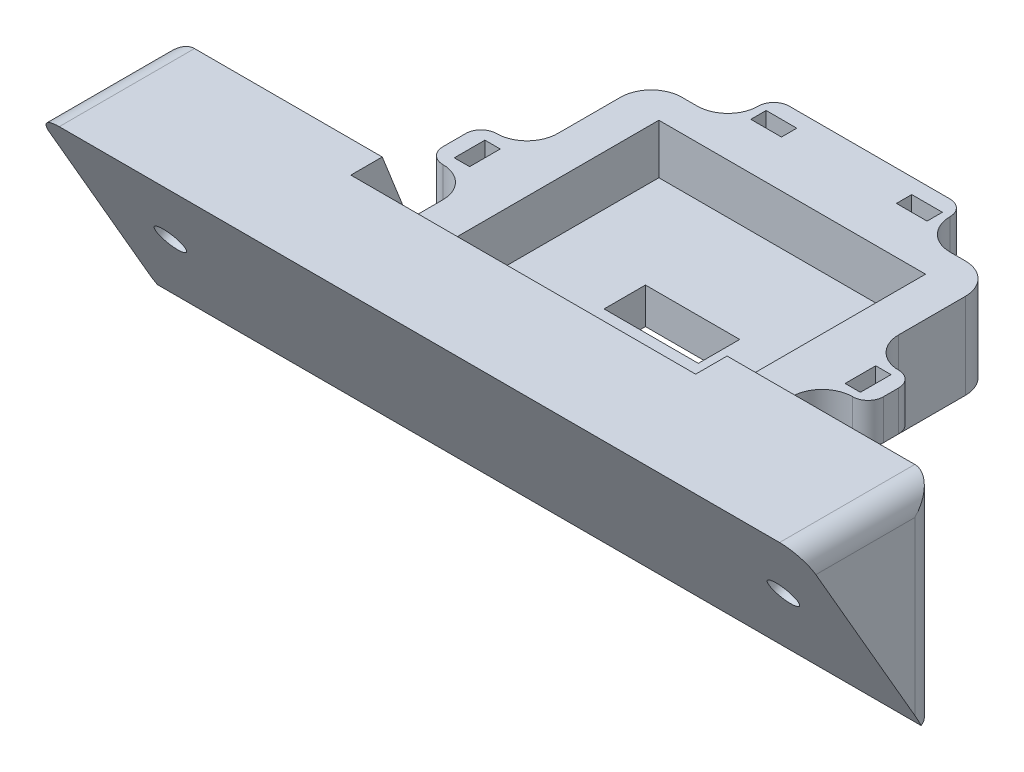
SolidWorks part; units mm, degrees
ref_plane "Front Plane" through (0, 0, 0) normal (0, 0, 1) x (1, 0, 0)
ref_plane "Top Plane" through (0, 0, 0) normal (0, 1, 0) x (1, 0, 0)
ref_plane "Right Plane" through (0, 0, 0) normal (1, 0, 0) x (0, 0, -1)
sketch "Sketch2" plane through (0, 0, 0) normal (0, 1, 0) x (1, 0, 0)
  line L1 (0, 0) -> (57.15, 0)
  line L2 (0, 0) -> (0, 49.784)
  line L3 (0, 49.784) -> (57.15, 49.784)
  line L4 (57.15, 0) -> (57.15, 49.784)
  dimension "D1" = 57.15
  dimension "D2" = 49.784
extrude "Boss-Extrude1" add sketch "Sketch2" along normal blind 14.224
sketch "Sketch3" plane through (0, 14.224, 0) normal (0, 1, 0) x (1, 0, 0)
  line L0 (0, 49.784) -> (0, 0) construction
  line L1 (6.477, 44.577) -> (50.673, 44.577)
  line L2 (6.477, 44.577) -> (6.477, 5.207)
  line L3 (6.477, 5.207) -> (50.673, 5.207)
  line L4 (50.673, 44.577) -> (50.673, 5.207)
  line L5 (57.15, 49.784) -> (0, 49.784) construction
  point P6 (0, 24.892)
  point P7 (6.477, 24.892)
  point P10 (28.575, 49.784)
  point P11 (28.575, 44.577)
  dimension "D1" = 44.196
  dimension "D2" = 39.37
extrude "Cut-Extrude1" cut sketch "Sketch3" against normal blind 8.255
sketch "Sketch4" plane through (0, 5.969, 0) normal (0, 1, 0) x (1, 0, 0)
  line L1 (10.795, 14.605) -> (46.355, 14.605)
  line L2 (10.795, 14.605) -> (10.795, 10.414)
  line L3 (10.795, 10.414) -> (46.355, 10.414)
  line L4 (46.355, 14.605) -> (46.355, 10.414)
  line L6 (6.477, 5.207) -> (50.673, 5.207) construction
  line L7 (50.673, 44.577) -> (6.477, 44.577) construction
  line L8 (20.7645, 28.067) -> (36.3855, 28.067)
  line L9 (20.7645, 28.067) -> (20.7645, 21.209)
  line L10 (20.7645, 21.209) -> (36.3855, 21.209)
  line L11 (36.3855, 28.067) -> (36.3855, 21.209)
  line L12 (6.477, 5.207) -> (50.673, 5.207) construction
  point P6 (28.575, 5.207)
  point P7 (28.575, 10.414)
  point P10 (28.575, 21.209)
  point P15 (28.575, 14.605)
  dimension "D1" = 35.56
  dimension "D3" = 9.398
  dimension "D4" = 4.191
  dimension "D5" = 15.621
  dimension "D6" = 6.858
  dimension "D7" = 16.51
extrude "Cut-Extrude2" cut sketch "Sketch4" against normal blind 8.255
sketch "Sketch5" plane through (0, 14.224, 0) normal (0, 1, 0) x (1, 0, 0)
  line L0 (0, 49.784) -> (0, 0) construction
  line L5 (57.15, 49.784) -> (0, 49.784) construction
  line L6 (0, 29.21) -> (-7.62, 29.21)
  line L7 (0, 29.21) -> (0, 20.32)
  line L8 (0, 20.32) -> (-7.62, 20.32)
  line L9 (-7.62, 29.21) -> (-7.62, 20.32)
  line L10 (12.7, 49.784) -> (36.83, 49.784)
  line L11 (12.7, 49.784) -> (12.7, 57.404)
  line L12 (12.7, 57.404) -> (36.83, 57.404)
  line L15 (36.83, 49.784) -> (44.45, 49.784)
  line L17 (36.83, 57.404) -> (44.45, 57.404)
  line L18 (44.45, 49.784) -> (44.45, 57.404)
  line L23 (57.15, 0) -> (57.15, 49.784) construction
  line L24 (57.15, 28.575) -> (64.77, 28.575)
  line L25 (57.15, 28.575) -> (57.15, 20.955)
  line L26 (57.15, 20.955) -> (64.77, 20.955)
  line L27 (64.77, 28.575) -> (64.77, 20.955)
  line L29 (0, 0) -> (57.15, 0) construction
  point P1 (0, 24.765)
  point P2 (57.15, 24.765)
  dimension "D1" = 8.89
  dimension "D2" = 7.62
  dimension "D3" = 29.21
  dimension "D4" = 12.7
  dimension "D5" = 12.7
extrude "Boss-Extrude2" add sketch "Sketch5" against normal blind 6.604
sketch "Sketch6" plane through (0, 14.224, 0) normal (0, 1, 0) x (1, 0, 0)
  line L1 (-5.08, 27.305) -> (-2.54, 27.305)
  line L2 (-5.08, 27.305) -> (-5.08, 22.225)
  line L3 (-5.08, 22.225) -> (-2.54, 22.225)
  line L4 (-2.54, 27.305) -> (-2.54, 22.225)
  line L13 (59.69, 27.305) -> (62.23, 27.305)
  line L14 (59.69, 27.305) -> (59.69, 22.225)
  line L15 (59.69, 22.225) -> (62.23, 22.225)
  line L16 (62.23, 27.305) -> (62.23, 22.225)
  line L18 (-7.62, 29.21) -> (-7.62, 20.32) construction
  line L19 (64.77, 20.955) -> (64.77, 28.575) construction
  line L20 (44.45, 57.404) -> (12.7, 57.404) construction
  line L22 (13.97, 54.864) -> (19.05, 54.864)
  line L23 (13.97, 54.864) -> (13.97, 52.324)
  line L24 (13.97, 52.324) -> (19.05, 52.324)
  line L25 (19.05, 54.864) -> (19.05, 52.324)
  line L26 (0, 49.784) -> (0, 29.21) construction
  line L30 (57.15, 28.575) -> (57.15, 49.784) construction
  line L31 (38.1, 54.864) -> (43.18, 54.864)
  line L32 (38.1, 54.864) -> (38.1, 52.324)
  line L33 (38.1, 52.324) -> (43.18, 52.324)
  line L34 (43.18, 54.864) -> (43.18, 52.324)
  point P28 (-7.62, 24.765)
  point P29 (-5.08, 24.765)
  point P30 (-2.54, 24.765)
  point P31 (59.69, 24.765)
  dimension "D1" = 5.08
  dimension "D2" = 2.54
  dimension "D3" = 5.08
  dimension "D4" = 2.54
  dimension "D5" = 5.08
  dimension "D6" = 2.54
  dimension "D7" = 2.54
  dimension "D8" = 2.54
  dimension "D9" = 2.54
  dimension "D10" = 2.54
  dimension "D11" = 2.54
  dimension "D12" = 5.08
  dimension "D13" = 13.97
  dimension "D14" = 13.97
extrude "Cut-Extrude3" cut sketch "Sketch6" against normal blind 6.604
fillet "Fillet1" radius 5.08 4 edges at (0, 7.112, -49.784) (0, 7.112, 0) (57.15, 7.112, 0) (57.15, 7.112, -49.784)
fillet "Fillet2" radius 2.54 6 edges at (64.77, 10.922, -20.955) (64.77, 10.922, -28.575) (-7.62, 10.922, -20.32) (-7.62, 10.922, -29.21) (44.45, 10.922, -57.404) (12.7, 10.922, -57.404)
sketch "Sketch7" plane through (0, 0, 0) normal (0, 0, 1) x (1, 0, 0)
  line L0 (-34.925, 14.224) -> (92.075, 14.224)
  line L1 (92.075, 14.224) -> (92.075, 0)
  line L2 (92.075, 0) -> (-34.925, 0)
  line L3 (-34.925, 0) -> (-34.925, 14.224)
  line L4 (5.08, 14.224) -> (52.07, 14.224) construction
  line L5 (5.08, 0) -> (52.07, 0) construction
  circle A0 centre (-30.861, 7.112) radius 2.3813
  circle A1 centre (88.011, 7.112) radius 2.3813
  point P9 (28.575, 0)
  point P10 (28.575, 0)
  point P18 (-34.925, 7.112)
  dimension "D1" = 4.7625
  dimension "D2" = 4.064
  dimension "D3" = 4.064
  dimension "D4" = 127
extrude "Boss-Extrude3" add sketch "Sketch7" against normal up to surface (5.207 mm away) up to face at (28.575, 10.0965, -5.207)
sketch "Sketch8" plane through (-34.925, 0, 0) normal (-1, 0, 0) x (0, 0, 1)
  line L1 (0, 25.4) -> (14.6647, 25.4)
  line L2 (14.6647, 25.4) -> (0, 0)
  line L3 (0, 0) -> (-5.207, 0)
  line L5 (0, 25.4) -> (0, 14.224)
  line L6 (0, 14.224) -> (0, 0) construction
  line L7 (0, 14.224) -> (-5.207, 14.224)
  line L8 (-5.207, 14.224) -> (-5.207, 0)
  dimension "D1" = 60
  dimension "D2" = 25.4
extrude "Boss-Extrude4" add sketch "Sketch8" against normal up to surface (127 mm away) up to face at (92.075, 7.112, -2.6035)
sketch "Sketch11" plane through (0, 0, 0) normal (0, 0, -1) x (-1, 0, 0)
  line L0 (34.925, 14.224) -> (-92.075, 14.224) construction
  line L1 (34.925, 25.4) -> (0, 25.4)
  line L2 (34.925, 25.4) -> (34.925, 14.224)
  line L3 (34.925, 14.224) -> (0, 14.224)
  line L4 (0, 25.4) -> (0, 14.224)
  line L6 (-92.075, 25.4) -> (-57.15, 25.4)
  line L7 (-92.075, 25.4) -> (-92.075, 14.224)
  line L8 (-92.075, 14.224) -> (-57.15, 14.224)
  line L9 (-57.15, 25.4) -> (-57.15, 14.224)
  point P12 (0, 0)
extrude "Boss-Extrude5" add sketch "Sketch11" along normal up to surface (5.207 mm away) up to face at (74.6125, 7.112, -5.207)
sketch "Sketch9" plane through (0, 0, 0) normal (0, -0.5, 0.866) x (1, 0, 0)
  line L2 (92.075, 29.3294) -> (-34.925, 29.3294) construction
  line L3 (-22.225, 11.5494) -> (79.375, 11.5494) construction
  line L4 (-34.925, 0) -> (92.075, 0) construction
  circle A0 centre (-22.225, 11.5494) radius 2.413
  circle A1 centre (79.375, 11.5494) radius 2.413
  point P6 (28.575, 0)
  point P7 (28.575, 11.5494)
  dimension "D1" = 4.826
  dimension "D2" = 101.6
  dimension "D4" = 17.78
extrude "Cut-Extrude4" cut sketch "Sketch9" against normal mid plane 50.8
fillet "Fillet3" radius 5.08 2 edges at (44.45, 10.922, -49.784) (12.7, 10.922, -49.784)
fillet "Fillet4" radius 5.08 4 edges at (57.15, 10.922, -20.955) (57.15, 10.922, -28.575) (0, 10.922, -29.21) (0, 10.922, -20.32)
sketch "Sketch12" plane through (0, 0, 0) normal (-1, 0, 0) x (0, 0, 1)
  line L0 (-5.207, 25.4) -> (-15.24, 0)
  line L1 (-44.704, 0) -> (-5.207, 0) construction
  line L2 (-15.24, 0) -> (-5.207, 0)
  line L3 (-5.207, 0) -> (-5.207, 25.4)
  point P5 (-15.522, 0)
extrude "Boss-Extrude6" add sketch "Sketch12" along normal blind 6.35
sketch "Sketch13" plane through (57.15, 0, 0) normal (1, 0, 0) x (0, 0, -1)
  line L0 (5.207, 25.4) -> (15.875, 0)
  line L1 (5.207, 0) -> (44.704, 0) construction
  line L2 (15.875, 0) -> (5.207, 0)
  line L3 (5.207, 0) -> (5.207, 25.4)
  point P5 (0, 0)
extrude "Boss-Extrude7" add sketch "Sketch13" along normal blind 6.35
sketch "Sketch14" plane through (-34.925, 0, 0) normal (-1, 0, 0) x (0, 0, 1)
  line L0 (-5.207, 0) -> (-5.207, -9.0188)
  line L1 (-5.207, -9.0188) -> (0, 0)
  line L2 (0, 0) -> (-5.207, 0)
  line L3 (0, 0) -> (14.6647, 25.4) construction
extrude "Boss-Extrude8" add sketch "Sketch14" against normal up to surface (127 mm away) up to face at (92.075, 12.7, 1.0627)
sketch "Sketch15" plane through (92.075, 0, 0) normal (1, 0, 0) x (0, 0, -1)
  line L0 (5.207, -9.0188) -> (2.667, -9.0188)
  line L1 (2.667, -9.0188) -> (-17.2047, 25.4)
  line L2 (-17.2047, 25.4) -> (-14.6647, 25.4)
  line L3 (-14.6647, 25.4) -> (5.207, -9.0188)
  dimension "D1" = 2.54
extrude "Boss-Extrude9" add sketch "Sketch15" against normal up to surface (127 mm away) up to face at (-34.925, 13.9271, 1.4169)
sketch "Sketch16" plane through (0, 0, 0) normal (0, 0.5, -0.866) x (-1, 0, 0)
  circle A0 centre (-79.375, 11.5494) radius 2.413
  circle A1 centre (22.225, 11.5494) radius 2.413
  circle A2 centre (-79.375, 11.5494) radius 2.413 construction
  circle A3 centre (22.225, 11.5494) radius 2.413 construction
extrude "Cut-Extrude6" cut sketch "Sketch16" against normal up to surface (2.1997 mm away) up to face at (28.575, 8.1906, 7.2688)
sketch "Sketch17" plane through (0, -1.0999, 1.905) normal (0, -0.5, 0.866) x (1, 0, 0)
  circle A0 centre (79.375, 11.5494) radius 5.08
  circle A1 centre (-22.225, 11.5494) radius 5.08
  dimension "D1" = 10.16
  dimension "D2" = 10.16
extrude "Cut-Extrude9" cut sketch "Sketch17" along normal offset from surface (17.78 mm away) 10.16 from offset 27.94 up to face at (79.375, 6.8125, 6.4732) offset against normal yes
fillet "Fillet5" radius 3.81 4 edges at (92.075, 25.4, 5.9988) (92.075, 8.1906, -5.207) (-34.925, 25.4, 5.9988) (-34.925, 8.1906, -5.207)
